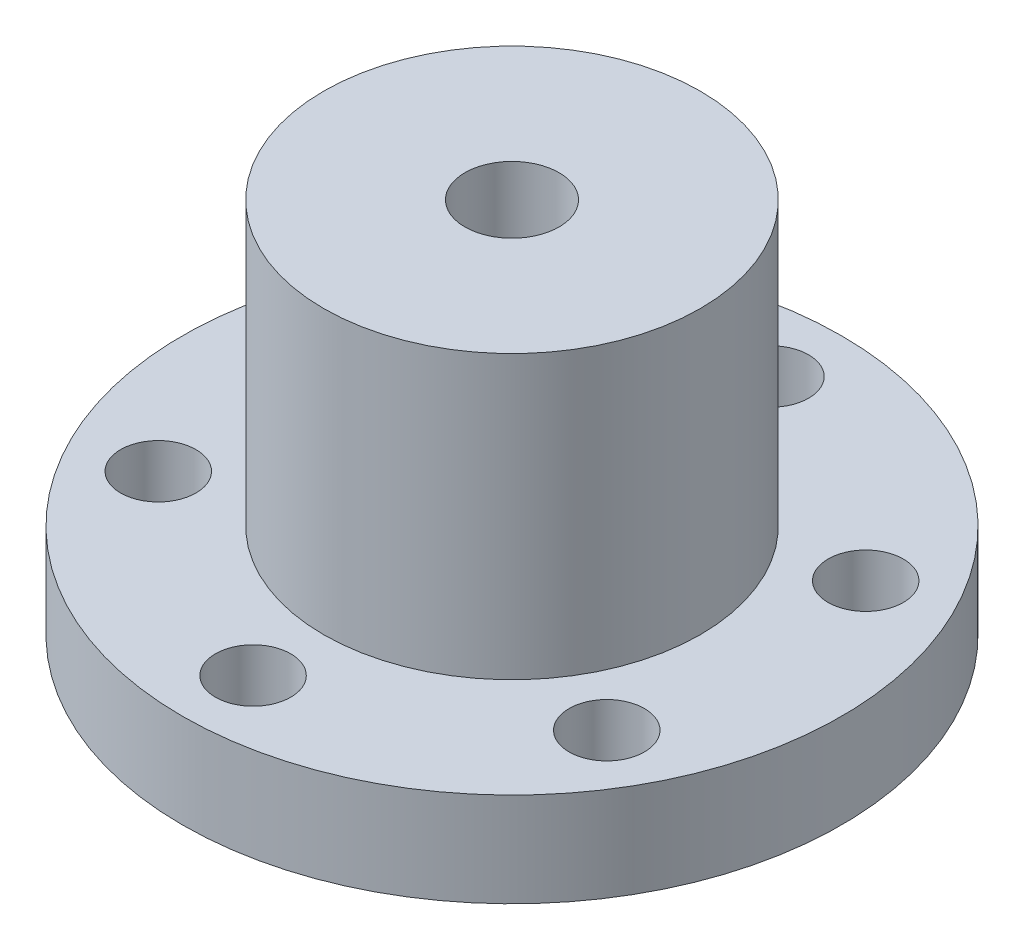
SolidWorks part; units mm, degrees
ref_plane "Front Plane" through (0, 0, 0) normal (0, 0, 1) x (1, 0, 0)
ref_plane "Top Plane" through (0, 0, 0) normal (0, 1, 0) x (1, 0, 0)
ref_plane "Right Plane" through (0, 0, 0) normal (1, 0, 0) x (0, 0, -1)
sketch "Sketch2" plane through (0, 0, 0) normal (0, 1, 0) x (1, 0, 0)
  circle A0 centre (0, 0) radius 17.5
  circle A1 centre (0, 0) radius 13.75 construction
  circle A2 centre (0, 13.75) radius 2
  circle A3 centre (11.9078, 6.875) radius 2
  circle A4 centre (11.9078, -6.875) radius 2
  circle A5 centre (0, -13.75) radius 2
  circle A6 centre (-11.9078, -6.875) radius 2
  circle A7 centre (-11.9078, 6.875) radius 2
  point P18 (0, 0)
  dimension "D1" = 35
  dimension "D2" = 27.5
  dimension "D3" = 4
  dimension "D4" = 6
extrude "Boss-Extrude1" add sketch "Sketch2" along normal blind 5
sketch "Sketch3" plane through (0, 5, 0) normal (0, 1, 0) x (1, 0, 0)
  circle A0 centre (0, 0) radius 10
  dimension "D1" = 20
extrude "Boss-Extrude2" add sketch "Sketch3" along normal blind 15
sketch "Sketch4" plane through (0, 20, 0) normal (0, 1, 0) x (1, 0, 0)
  circle A0 centre (0, 0) radius 2.5
  dimension "D1" = 5
extrude "Cut-Extrude1" cut sketch "Sketch4" against normal through all
